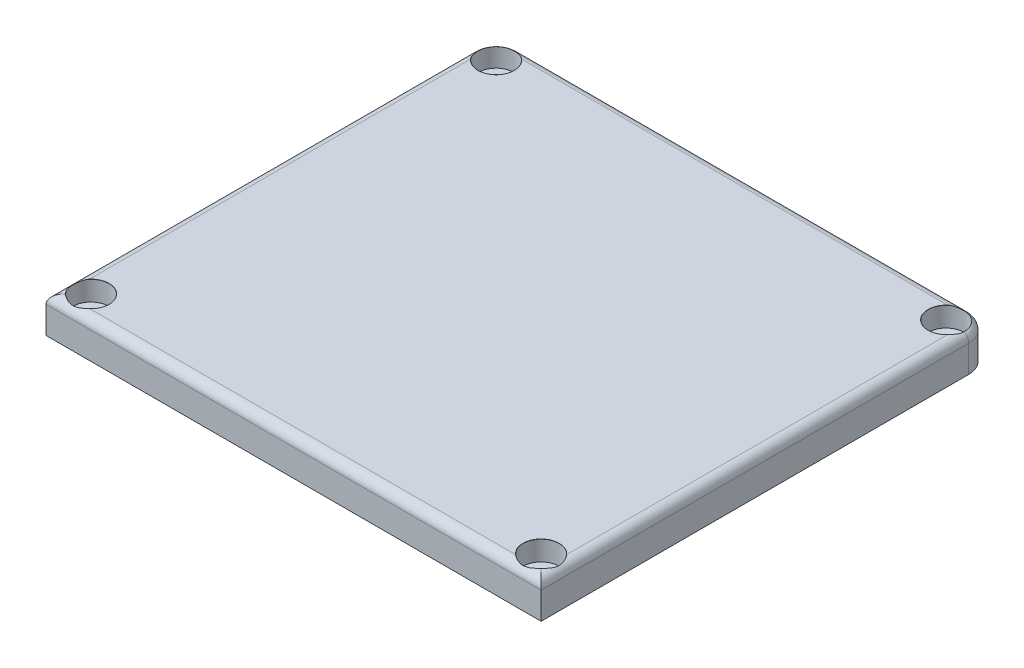
SolidWorks part; units mm, degrees
ref_plane "Front Plane" through (0, 0, 0) normal (0, 0, 1) x (1, 0, 0)
ref_plane "Top Plane" through (0, 0, 0) normal (0, 1, 0) x (1, 0, 0)
ref_plane "Right Plane" through (0, 0, 0) normal (1, 0, 0) x (0, 0, -1)
sketch "Sketch2" plane through (0, 0, 0) normal (0, 1, 0) x (1, 0, 0)
  line L1 (-55, 50) -> (55, 50)
  line L2 (-55, 50) -> (-55, -50)
  line L3 (-55, -50) -> (55, -50)
  line L4 (55, 50) -> (55, -50)
  line L5 (-55, 50) -> (55, -50) construction
  line L6 (-55, -50) -> (55, 50) construction
  point P0 (0, 0)
  dimension "D1" = 110
  dimension "D2" = 100
extrude "Boss-Extrude1" add sketch "Sketch2" along normal blind 8
fillet "Fillet2" radius 2 4 edges at (0, 8, -50) (55, 8, 0) (0, 8, 50) (-55, 8, 0)
fillet "Fillet3" radius 5 4 edges at (-54.4142, 7.4142, -49.4142) (54.4142, 7.4142, -49.4142) (55, 3, -50) (-55, 3, -50)
hole_wizard "CBORE for M4 Hex Socket Head Cap Screw1" positions "Sketch3" profile "Sketch4" counterbore size "M4" standard "ISO"
sketch "Sketch3" plane through (0, 8, 0) normal (0, -1, 0) x (-1, 0, 0)
  line L0 (-55, 0) -> (55, 0)
  line L1 (-55, -50) -> (-55, 45) construction
  line L2 (55, 45) -> (55, -50) construction
  point P0 (-50, 45)
  point P3 (50, 45)
  point P16 (50, -45)
  point P17 (-50, -45)
sketch "Sketch4" plane through (50, 8, -45) normal (1, 0, 0) x (0, 0, 1)
  line L0 (0, 0) -> (0, 11.4519)
  line L1 (0, 11.4519) -> (2.25, 10.1)
  line L2 (2.25, 10.1) -> (2.25, 4.4)
  line L3 (2.25, 4.4) -> (4, 4.4)
  line L5 (4, 4.4) -> (4, 0.025)
  line L6 (4, 0.025) -> (4.025, 0)
  line L7 (4.025, 0) -> (0, 0)
  line L8 (-4, 0.025) -> (-4.025, 0) construction
  line L10 (0, 11.4519) -> (-2.25, 10.1) construction
  line L11 (0, -6.35) -> (0, 107.95) construction
  dimension "Hole Dia." = 4.5
  dimension "Hole Depth" = 10.1
  dimension "C'Bore Dia." = 8
  dimension "C'Bore Depth" = 4.4
  dimension "Near C'Sink Dia." = 8.05
  dimension "Near C'Sink Angle" = 90
  dimension "Drill Angle" = 118
